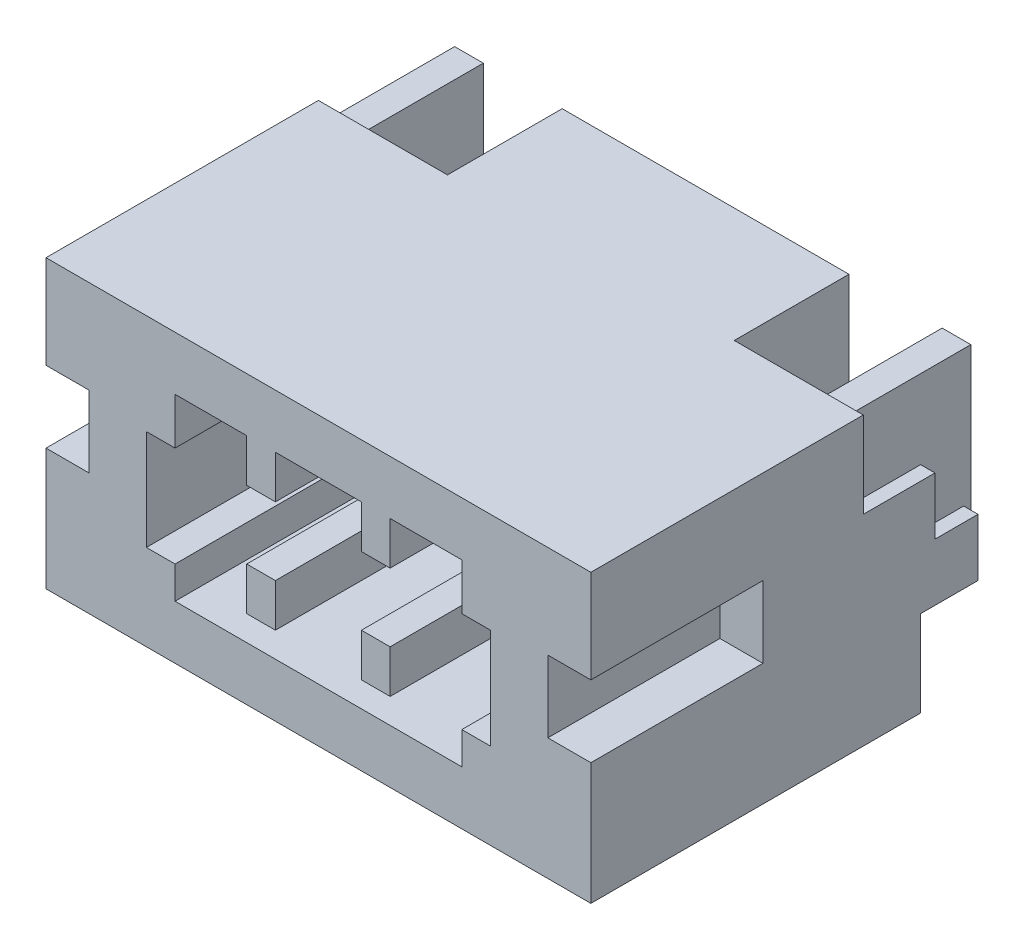
SolidWorks part; units mm, degrees
ref_plane "Ebene vorne" through (0, 0, 0) normal (0, 0, 1) x (1, 0, 0)
ref_plane "Ebene oben" through (0, 0, 0) normal (0, 1, 0) x (1, 0, 0)
ref_plane "Ebene rechts" through (0, 0, 0) normal (1, 0, 0) x (0, 0, -1)
sketch "Skizze1" plane through (0, 0, 0) normal (0, 0, 1) x (1, 0, 0)
  line L1 (-1.9, -1) -> (1.9, -1)
  line L2 (-1.9, -1) -> (-1.9, 1)
  line L3 (-1.9, 1) -> (1.9, 1)
  line L4 (1.9, -1) -> (1.9, 1)
  line L5 (-1.9, -1) -> (1.9, 1) construction
  line L6 (-1.9, 1) -> (1.9, -1) construction
  point P0 (0, 0)
  dimension "D1" = 2
  dimension "D2" = 3.8
extrude "Aufsatz-Linear austragen1" add sketch "Skizze1" along normal blind 2.7
sketch "Skizze2" plane through (0, 0, 0) normal (1, 0, 0) x (0, 0, -1)
  line L1 (0, -1) -> (-0.4, -1)
  line L2 (0, -1) -> (0, -0.4)
  line L3 (0, -0.4) -> (-0.4, -0.4)
  line L4 (-0.4, -1) -> (-0.4, -0.4)
  dimension "D1" = 0.4
  dimension "D2" = 0.6
extrude "Schnitt-Linear austragen1" cut sketch "Skizze2" against normal through all both and the other way through all
sketch "Skizze3" plane through (0, 0, 0) normal (1, 0, 0) x (0, 0, -1)
  line L0 (-0.8, 1) -> (-0.8, 0.4)
  line L1 (-2.7, 1) -> (0, 1) construction
  line L2 (-0.8, 0.4) -> (-0.3, 0.4)
  line L3 (-0.3, 0.4) -> (-0.3, 0)
  line L4 (-0.3, 0) -> (0, 0)
  line L5 (0, -0.4) -> (0, 1) construction
  line L6 (-0.8, 1) -> (0, 1)
  line L7 (0, 1) -> (0, 0)
  dimension "D1" = 1
  dimension "D2" = 0.3
  dimension "D3" = 0.6
  dimension "D4" = 0.8
extrude "Schnitt-Linear austragen4" cut sketch "Skizze3" against normal through all from offset 1 offset against normal yes
sketch "Skizze4" plane through (0, 0, 0) normal (1, 0, 0) x (0, 0, -1)
  line L8 (-0.15, -0.4) -> (0.05, -0.6)
  line L9 (0.05, -0.6) -> (0.05, -1.2)
  line L10 (0.05, -1.2) -> (-0.1, -1.2)
  line L11 (-0.1, -1.2) -> (-0.1, -0.7328)
  line L12 (-0.1, -0.7328) -> (-0.4328, -0.4)
  line L13 (-0.4328, -0.4) -> (-0.15, -0.4)
  line L14 (-2.7, -1) -> (-0.4, -1) construction
  line L15 (0, -0.4) -> (0, 1) construction
  line L16 (0, -0.4) -> (-0.4, -0.4) construction
  point P2 (-0.4182, -0.5067)
  point P8 (-0.3854, -0.5108)
  point P13 (0, 0)
  dimension "D1" = 0.6
  dimension "D2" = 0.2
  dimension "D3" = 0.05
  dimension "D4" = 0.15
  dimension "D5" = 0.2
  dimension "D6" = 135
extrude "Aufsatz-Linear austragen2" add sketch "Skizze4" along normal mid plane 0.2 from offset 0.4 offset against normal yes
sketch "Skizze5" plane through (0, 0, 0) normal (0, 0, 1) x (1, 0, 0)
  line L1 (-1.6, 0.95) -> (-1.8, 0.95)
  line L2 (-1.6, 0.95) -> (-1.6, -0.05)
  line L3 (-1.6, -0.05) -> (-1.8, -0.05)
  line L4 (-1.8, 0.95) -> (-1.8, -0.05)
  point P4 (-1.7, 0.95)
  dimension "D1" = 0.2
  dimension "D2" = 1
  dimension "D3" = 1.7
  dimension "D4" = 0.95
extrude "Aufsatz-Linear austragen3" add sketch "Skizze5" along normal up to next and the other way blind 0.05
sketch "Skizze6" plane through (0, 0, 0) normal (0, 0, 1) x (1, 0, 0)
  line L1 (-1, -0.625) -> (1, -0.625)
  line L2 (-1, -0.625) -> (-1, 0.625)
  line L3 (-1, 0.625) -> (1, 0.625)
  line L4 (1, -0.625) -> (1, 0.625)
  line L5 (-1, -0.625) -> (1, 0.625) construction
  line L6 (-1, 0.625) -> (1, -0.625) construction
  line L7 (-0.5, 0.625) -> (-0.3, 0.625)
  line L8 (-0.5, 0.625) -> (-0.5, 0.325)
  line L9 (-0.5, 0.325) -> (-0.3, 0.325)
  line L10 (-0.3, 0.625) -> (-0.3, 0.325)
  line L11 (-0.5, -0.15) -> (-0.3, -0.15)
  line L12 (-0.5, -0.15) -> (-0.5, -0.45)
  line L13 (-0.5, -0.45) -> (-0.3, -0.45)
  line L14 (-0.3, -0.15) -> (-0.3, -0.45)
  line L15 (0.3, 0.625) -> (0.5, 0.625)
  line L16 (0.3, 0.625) -> (0.3, 0.325)
  line L17 (0.3, 0.325) -> (0.5, 0.325)
  line L18 (0.5, 0.625) -> (0.5, 0.325)
  line L19 (0.3, -0.15) -> (0.5, -0.15)
  line L20 (0.3, -0.15) -> (0.3, -0.45)
  line L21 (0.3, -0.45) -> (0.5, -0.45)
  line L22 (0.5, -0.15) -> (0.5, -0.45)
  point P0 (0, 0)
  point P22 (-0.4, 0.325)
  point P23 (0.4, 0.325)
  point P24 (0.5, -0.3)
  point P25 (0.2942, -0.0666)
  dimension "D1" = 2
  dimension "D2" = 1.25
  dimension "D3" = 0.2
  dimension "D4" = 0.4
  dimension "D5" = 0.4
  dimension "D6" = 0.3
  dimension "D7" = 0.3
  dimension "D8" = 0.3
extrude "Schnitt-Linear austragen5" cut sketch "Skizze6" along normal through all from offset 1 contours L3 L18 L17 L16 L10 L9 L8 L2 L1 L4 L11 L14 L13 L12 L19 L22 L21 L20 region at (0, -0.0093, 0)
sketch "Skizze7" plane through (0, 0, 0) normal (0, 0, 1) x (1, 0, 0)
  line L0 (-1, -0.625) -> (-1, 0.625) construction
  line L1 (-1, 0.3) -> (-1.2, 0.3)
  line L2 (-1, 0.3) -> (-1, -0.4)
  line L3 (-1, -0.4) -> (-1.2, -0.4)
  line L4 (-1.2, 0.3) -> (-1.2, -0.4)
  line L5 (1, -0.625) -> (1, 0.625) construction
  line L6 (1, 0.3) -> (1.2, 0.3)
  line L7 (1, 0.3) -> (1, -0.4)
  line L8 (1, -0.4) -> (1.2, -0.4)
  line L9 (1.2, 0.3) -> (1.2, -0.4)
  dimension "D1" = 2.4
  dimension "D2" = 0.7
  dimension "D3" = 0.4
extrude "Schnitt-Linear austragen6" cut sketch "Skizze7" along normal through all from offset 1
sketch "Skizze8" plane through (0, 0, 0) normal (0, 0, 1) x (1, 0, 0)
  line L0 (-1.9, 1) -> (-1.9, -1) construction
  line L1 (-1.9, 0.35) -> (-1.6, 0.35)
  line L2 (-1.9, 0.35) -> (-1.9, -0.15)
  line L3 (-1.9, -0.15) -> (-1.6, -0.15)
  line L4 (-1.6, 0.35) -> (-1.6, -0.15)
  line L5 (1.9, -1) -> (1.9, 1) construction
  line L6 (1.9, 0.35) -> (1.6, 0.35)
  line L7 (1.9, 0.35) -> (1.9, -0.15)
  line L8 (1.9, -0.15) -> (1.6, -0.15)
  line L9 (1.6, 0.35) -> (1.6, -0.15)
  point P12 (-1.6, 0.1)
  dimension "D1" = 0.5
  dimension "D2" = 0.1
  dimension "D3" = 0.3
  dimension "D4" = 0.3
extrude "Schnitt-Linear austragen7" cut sketch "Skizze8" along normal through all from offset 1.5
mirror "Spiegeln1" about plane through (0, 0, 0) normal (1, 0, 0) of "Aufsatz-Linear austragen3", "Schnitt-Linear austragen4", "Aufsatz-Linear austragen2"
